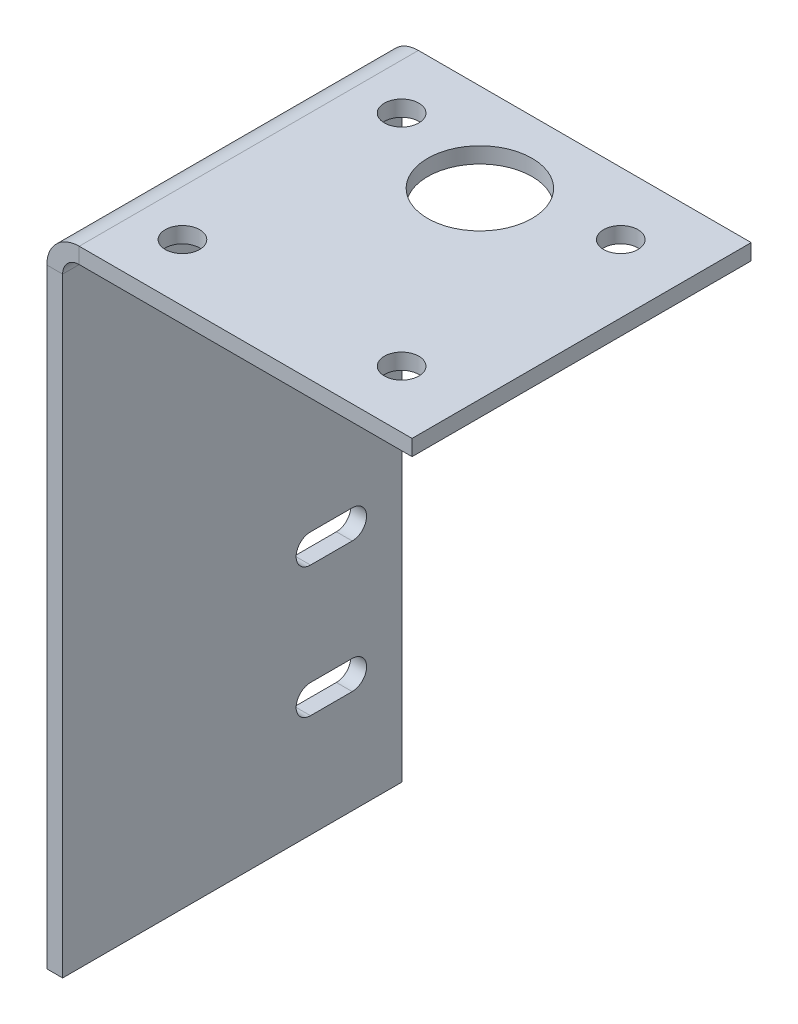
SolidWorks part; units mm, degrees
note: The reader was unsure of these and kept them because the rebuilt part matched: flange length of "Edge-Flange1".
material "Low Carbon Steel"
ref_plane "Front Plane" through (0, 0, 0) normal (0, 0, 1) x (1, 0, 0)
ref_plane "Top Plane" through (0, 0, 0) normal (0, 1, 0) x (1, 0, 0)
ref_plane "Right Plane" through (0, 0, 0) normal (1, 0, 0) x (0, 0, -1)
sketch "Sketch1" plane through (0, 0, 0) normal (0, 1, 0) x (1, 0, 0)
  line L1 (0, 32.5) -> (70, 32.5)
  line L2 (0, 32.5) -> (0, -32.5)
  line L3 (0, -32.5) -> (70, -32.5)
  line L4 (70, 32.5) -> (70, -32.5)
  dimension "D1" = 65
  dimension "D2" = 70
base flange "Base-Flange1" sketch "Sketch1" thickness 3.0378 reverse thickness direction no parameters "D1"=3.175
edge flange "Edge-Flange1" sketch "Sketch8" flange angle 90 flange length 120 flange position material inside bend radius 3.175 thickness 3.0378 relief rectangular parameters "D6"=10
sketch "Sketch8" plane through (0, -3.0378, 0) normal (-1, 0, 0) x (0, 0, -1)
  line L0 (32.5, 0) -> (-32.5, 0) construction
  line L1 (32.5, 0) -> (-32.5, 0)
  line L2 (-32.5, 0) -> (-32.5, 120)
  line L3 (-32.5, 120) -> (32.5, 120)
  line L4 (32.5, 120) -> (32.5, 0)
bend "EdgeBend1" bend radius 3.175 bend angle 90 parameters "D5"=1
sketch "Sketch9" plane through (0, 0, 0) normal (-1, 0, 0) x (0, 0, 1)
  line L0 (-23, -75.5) -> (-15, -75.5) construction
  line L1 (-23, -72.75) -> (-15, -72.75)
  line L2 (-23, -78.25) -> (-15, -78.25)
  line L3 (-23, -100.5) -> (-15, -100.5) construction
  line L4 (-23, -97.75) -> (-15, -97.75)
  line L5 (-23, -103.25) -> (-15, -103.25)
  line L6 (-19, -75.5) -> (-19, -100.5) construction
  line L7 (-32.5, -6.2128) -> (-32.5, -123.0378) construction
  line L8 (-32.5, 0) -> (32.5, 0) construction
  arc A0 (-23, -72.75) -> (-23, -78.25) centre (-23, -75.5) ccw
  arc A1 (-15, -78.25) -> (-15, -72.75) centre (-15, -75.5) ccw
  arc A2 (-23, -97.75) -> (-23, -103.25) centre (-23, -100.5) ccw
  arc A3 (-15, -103.25) -> (-15, -97.75) centre (-15, -100.5) ccw
  point P2 (-19, -75.5)
  point P7 (-19, -100.5)
  dimension "D1" = 25
  dimension "D2" = 5.5
  dimension "D3" = 8
  dimension "D4" = 13.5
  dimension "D5" = 75.5
extrude "Cut-Extrude1" cut sketch "Sketch9" against normal through all normal cut yes
ref_plane "switch center" through (0, -88, 0) normal (0, -1, 0) x (-1, 0, 0)
hole_wizard "M6 Clearance Hole1" positions "Sketch11" profile "Sketch10" hole size "M6" standard "Peddi DIN" end condition through all
sketch "Sketch11" plane through (0, 0, 0) normal (0, 1, 0) x (1, 0, 0)
  line L1 (57, 20.5) -> (57, -21.5) construction
  line L5 (0, 32.5) -> (0, -32.5) construction
  line L6 (70, 32.5) -> (6.2128, 32.5) construction
  point P0 (57, 20.5)
  point P4 (57, -21.5)
  point P6 (15, -21.5)
  point P32 (15, 20.5)
  dimension "D1" = 12
  dimension "D2" = 42
  dimension "D3" = 57
  dimension "D4" = 42
  dimension "D5" = 42
sketch "Sketch10" plane through (57, 0, -20.5) normal (1, 0, 0) x (0, 0, 1)
  line L0 (0, 0) -> (0, 123.0378)
  line L1 (0, 123.0378) -> (3.3, 123.0378)
  line L2 (3.3, 123.0378) -> (3.3, 0)
  line L5 (3.3, 0) -> (0, 0)
  line L11 (0, -6.35) -> (0, 107.95) construction
  dimension "Thru Hole Dia." = 6.6
  dimension "Thru Hole Depth" = 123.0378
sketch "Sketch12" plane through (0, -3.0378, 0) normal (0, -1, 0) x (1, 0, 0)
  circle A0 centre (35, -15.5) radius 10
  circle A2 centre (57, -20.5) radius 3.3 construction
  dimension "D1" = 20
  dimension "D2" = 5
  dimension "D3" = 22
extrude "Cut-Extrude2" cut sketch "Sketch12" against normal blind 3.0378 normal cut yes
other "Freeze***"
sketch "Bend-Lines1" [suppressed] plane through (0, 0, 0) normal (0, 1, 0) x (1, 0, 0)
sketch "Bounding-Box1" [suppressed] plane through (0, 0, 0) normal (0, 1, 0) x (1, 0, 0)
sheet metal parameters "Sheet-Metal16" thickness 3.0378 parameters "D1"=3.175
flat pattern "Flat-Pattern16" [suppressed]
sketch "Bend-Lines2" plane through (0, 0, 0) normal (0, 1, 0) x (1, 0, 0)
sketch "Bounding-Box2" [suppressed] plane through (0, 0, 0) normal (0, 1, 0) x (1, 0, 0)
sheet metal parameters "Sheet-Metal17" thickness 3.0378 parameters "D1"=3.175
flat pattern "Flat-Pattern16" [suppressed]
sketch "Bend-Lines2" plane through (0, 0, 0) normal (0, 1, 0) x (1, 0, 0)
sketch "Bounding-Box2" [suppressed] plane through (0, 0, 0) normal (0, 1, 0) x (1, 0, 0)
bend of the flat pattern "Flatten-<EdgeBend1>1"
sheet metal parameters "Sheet-Metal18" thickness 3.0378 parameters "D1"=3.175
flat pattern "Flat-Pattern16" [suppressed]
sketch "Bend-Lines2" plane through (0, 0, 0) normal (0, 1, 0) x (1, 0, 0)
sketch "Bounding-Box2" [suppressed] plane through (0, 0, 0) normal (0, 1, 0) x (1, 0, 0)
bend of the flat pattern "Flatten-<EdgeBend1>1"
sheet metal parameters "Sheet-Metal19" thickness 3.0378 parameters "D1"=3.175
flat pattern "Flat-Pattern16" [suppressed]
sketch "Bend-Lines2" plane through (0, 0, 0) normal (0, 1, 0) x (1, 0, 0)
sketch "Bounding-Box2" [suppressed] plane through (0, 0, 0) normal (0, 1, 0) x (1, 0, 0)
bend of the flat pattern "Flatten-<EdgeBend1>1"
sheet metal parameters "Sheet-Metal20" thickness 3.0378 parameters "D1"=3.175
flat pattern "Flat-Pattern16"
sketch "Bend-Lines2" plane through (0, 0, 0) normal (0, 1, 0) x (1, 0, 0)
  line L0 (2.7648, 32.5) -> (2.7648, -32.5) construction
  line L1 (2.7648, 32.5) -> (2.7648, -32.5) construction
sketch3d "Bounding-Box2" [suppressed]
  line L0 (70, -32.5, 0) -> (-117.5082, -32.5, 0) construction
  line L1 (70, 32.5, 0) -> (-117.5082, 32.5, 0) construction
  line L2 (70, -32.5, 0) -> (70, 32.5, 0) construction
  line L3 (-117.5082, -32.5, 0) -> (-117.5082, 32.5, 0) construction
bend of the flat pattern "Flatten-<EdgeBend1>1"
